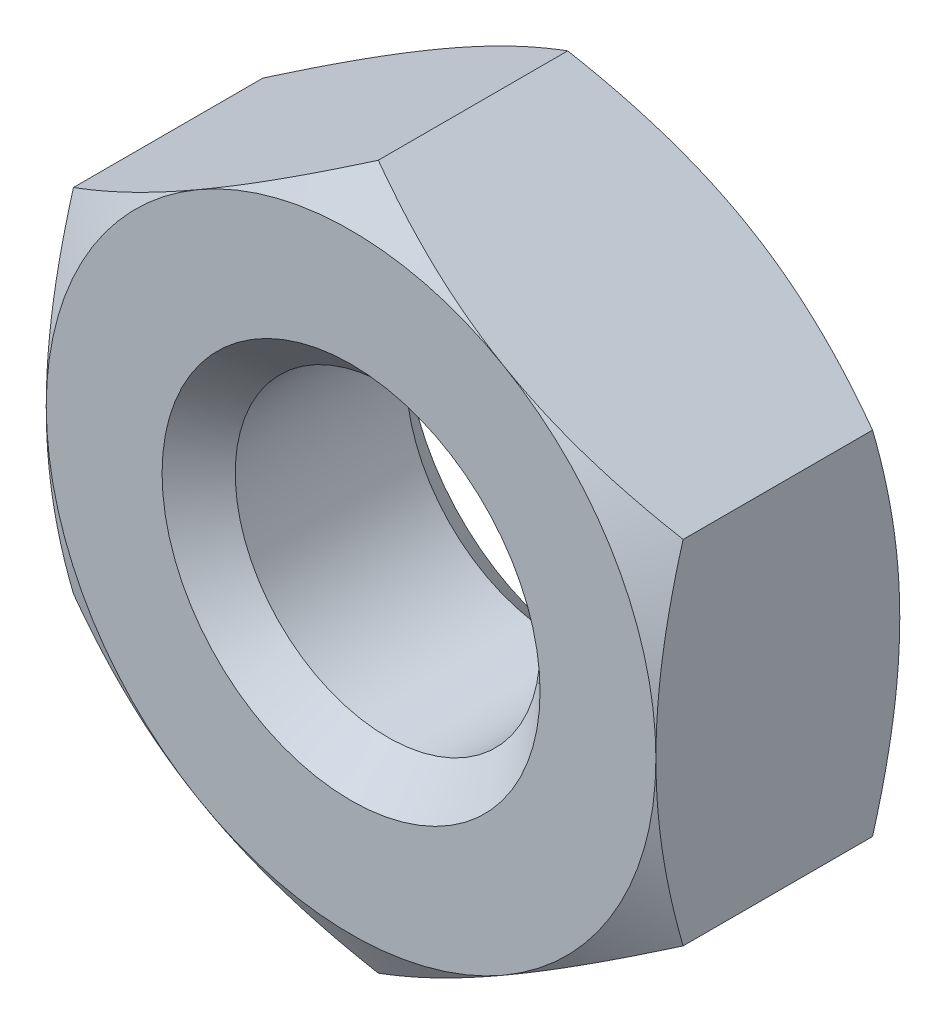
SolidWorks part; units mm, degrees
material "AISI Type A2 Tool Steel"
ref_plane "Front Plane" through (0, 0, 0) normal (0, 0, 1) x (1, 0, 0)
ref_plane "Top Plane" through (0, 0, 0) normal (0, 1, 0) x (1, 0, 0)
ref_plane "Right Plane" through (0, 0, 0) normal (1, 0, 0) x (0, 0, -1)
sketch "Sketch1" plane through (0, 0, 0) normal (0, 0, 1) x (1, 0, 0)
  line L1 (0, 2.8868) -> (-2.5, 1.4434)
  line L2 (-2.5, 1.4434) -> (-2.5, -1.4434)
  line L3 (-2.5, -1.4434) -> (0, -2.8868)
  line L4 (0, -2.8868) -> (2.5, -1.4434)
  line L5 (2.5, -1.4434) -> (2.5, 1.4434)
  line L6 (2.5, 1.4434) -> (0, 2.8868)
  circle A0 centre (0, 0) radius 2.5 construction
  circle A1 centre (0, 0) radius 1.25
  circle A3 centre (0, 0) radius 3.5
  dimension "D1" = 7
  dimension "D2" = 5
  dimension "D3" = 2.5
extrude "Boss-Extrude1" add sketch "Sketch1" along normal blind 2 contours A3 L6 L5 L4 L3 L2 L1 | L5 L6 L1 L2 L3 L4 A1 region at (1.2118, 2.0989, 0) region at (-3.401, 0, 0)
chamfer "Chamfer1" distance 1 angle 30 1 edges at (3.5, 0, 2) first distance on face at (3.5, 0, 2)
chamfer "Chamfer2" distance 1 angle 30 1 edges at (3.5, 0, 0) first distance on face at (3.5, 0, 0)
extrude "Cut-Extrude1" cut sketch "Sketch1<3>" along normal through all contours A3 L6 L5 L4 L3 L2 L1 region at (-3.401, 0, 0)
sketch "Sketch1<3>" plane through (0, 0, 0) normal (0, 0, 1) x (1, 0, 0) same geometry as "Sketch1"
chamfer "Chamfer3" distance 0.3 angle 45 2 edges at (1.25, 0, 0) (1.25, 0, 2)
